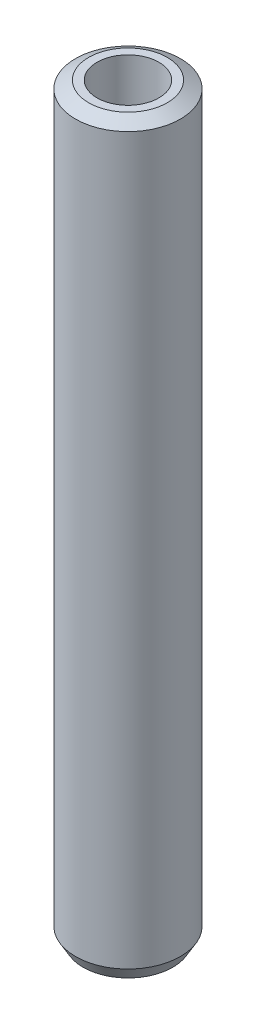
SolidWorks part; units mm, degrees
ref_plane "Front Plane" through (0, 0, 0) normal (0, 0, 1) x (1, 0, 0)
ref_plane "Top Plane" through (0, 0, 0) normal (0, 1, 0) x (1, 0, 0)
ref_plane "Right Plane" through (0, 0, 0) normal (1, 0, 0) x (0, 0, -1)
sketch "Sketch1" plane through (0, 0, 0) normal (0, 1, 0) x (1, 0, 0)
  circle A0 centre (0, 0) radius 15
  dimension "SHAFT_OD" = 30
extrude "Boss-Extrude1" add sketch "Sketch1" along normal blind 213.3399
sketch "Sketch2" plane through (0, 0, 0) normal (0, 1, 0) x (1, 0, 0)
  circle A0 centre (0, 0) radius 8.8475
  dimension "BORE_D" = 17.695
extrude "Cut-Extrude1" cut sketch "Sketch2" along normal through all
chamfer "Chamfer1" distance 2.1665 angle 60 2 edges at (0, 213.3399, 15) (0, 0, 15) first distance on face at (0, 213.3399, 15) first distance on face at (0, 0, 8.8475)
